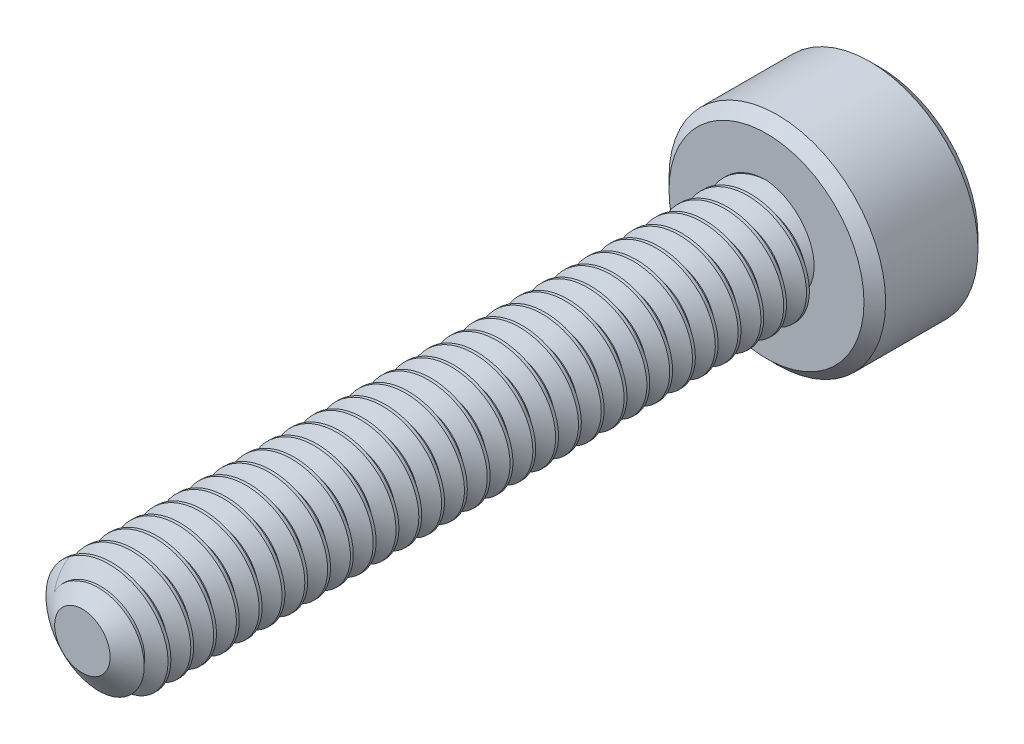
SolidWorks part; units mm, degrees
other "DetailItem1"
ref_plane "Front Plane" through (0, 0, 0) normal (0, 0, 1) x (1, 0, 0)
ref_plane "Top Plane" through (0, 0, 0) normal (0, 1, 0) x (1, 0, 0)
ref_plane "Right Plane" through (0, 0, 0) normal (1, 0, 0) x (0, 0, -1)
sketch "Sketch1" plane through (0, 0, 0) normal (0, 0, 1) x (1, 0, 0)
  circle A0 centre (0, 0) radius 1
  dimension "OD" = 2
extrude "Extrude1" add sketch "Sketch1" against normal blind 12
sketch "Sketch2" plane through (0, 0, 0) normal (0, 0, 1) x (1, 0, 0)
  circle A0 centre (0, 0) radius 1 construction
  circle A1 centre (0, 0) radius 1
curve "Helix/Spiral1" pitch 0.4 height 12.4 turns 31 parameters "pitch"=0.4
sketch "Sketch3" plane through (0, 0, 0) normal (1, 0, 0) x (0, 0, -1)
  line L0 (-0.35, 1) -> (-0.2, 0.7402)
  line L1 (-0.2, 0.7402) -> (-0.15, 0.7402)
  line L2 (-0.15, 0.7402) -> (0, 1)
  line L3 (-0.35, 1) -> (0, 1)
  line L4 (-0.175, 1) -> (-0.175, 0.7402) construction
  line L5 (-0.275, 0.8701) -> (-0.075, 0.8701) construction
  line L6 (0, 1) -> (0, -1) construction
  dimension "D1" = 0.05
  dimension "D2" = 0.2
  dimension "D3" = 60
sweep "Cut-Sweep1" cut profiles "Sketch3" path "Helix/Spiral1"
sketch "Sketch4" plane through (0, 0, 0) normal (1, 0, 0) x (0, 0, -1)
  line L0 (0.3598, 1) -> (0, 0.4862)
  line L1 (0, 0.4862) -> (0, 1)
  line L2 (0.3598, 1) -> (0, 1)
  line L3 (-0.35, 1) -> (0, 1) construction
  line L4 (0, 0) -> (7.0209, 0) construction
  dimension "D1" = 55
  dimension "D2" = 0.254
revolve "Cut-Revolve1" cut sketch "Sketch4" angle 360 about L4
sketch "Sketch6" plane through (0, 0, -12) normal (0, 0, -1) x (-1, 0, 0)
  circle A0 centre (0, 0) radius 1.9
  dimension "head dia" = 3.8
extrude "Extrude2" add sketch "Sketch6" along normal blind 2
sketch "Sketch7" plane through (0, 0, -14) normal (0, 0, -1) x (-1, 0, 0)
  line L1 (0, 0.866) -> (-0.75, 0.433)
  line L2 (-0.75, 0.433) -> (-0.75, -0.433)
  line L3 (-0.75, -0.433) -> (0, -0.866)
  line L4 (0, -0.866) -> (0.75, -0.433)
  line L5 (0.75, -0.433) -> (0.75, 0.433)
  line L6 (0.75, 0.433) -> (0, 0.866)
  circle A0 centre (0, 0) radius 0.75 construction
  dimension "hex dia" = 1.5
extrude "Cut-Extrude1" cut sketch "Sketch7" against normal blind 1.125
sketch "Sketch8" plane through (0, 0, -14) normal (0, 0, -1) x (-1, 0, 0)
  circle A0 centre (0, 0) radius 0.866
extrude "Cut-Extrude2" cut sketch "Sketch8" against normal through all draft 45
chamfer "Chamfer1" distance 0.19 angle 45 2 edges at (-1.9, 0, -14) (-1.9, 0, -12)
sketch "Sketch10" plane through (0, 0, -12) normal (0, 0, 1) x (1, 0, 0)
  circle A1 centre (0, 0) radius 1
  circle A2 centre (0, 0) radius 1
  dimension "D1" = 0
ref_plane "Plane1" through (0, 0, 0) normal (0, 0, 1) x (1, 0, 0)
extrude "partial thread" [suppressed] add sketch "Sketch10" along normal up to surface (2 mm away) separate body
chamfer "Chamfer2" [suppressed] distance 0.04 angle 45
combine bodies "Combine1" [suppressed] operation type add bodies to combine 107 108
sketch "Sketch9" plane through (0, 0, 0) normal (1, 0, 0) x (0, 0, -1)
  line L0 (0, 1) -> (0, -1) construction
  line L1 (1, 1) -> (1, -1) construction
  dimension "D1" = 1
equation "\"D3@Helix/Spiral1\" = \"screw length@Extrude1\"+\"pitch@Helix/Spiral1\""
equation "\"D1@Sketch3\" = \"pitch@Helix/Spiral1\"*.125"
equation "\"D2@Sketch3\" = \"pitch@Helix/Spiral1\"*.5"
equation "\"D1@Cut-Extrude1\" = \"hex dia@Sketch7\"*.75"
equation "\"D1@Chamfer1\" = \"head dia@Sketch6\"*.05"
equation "\"D1@Sketch9\" = \"pitch@Helix/Spiral1\"*2.5"
equation "\"D1@Chamfer2\"=\"OD@Sketch1\"*.02"
